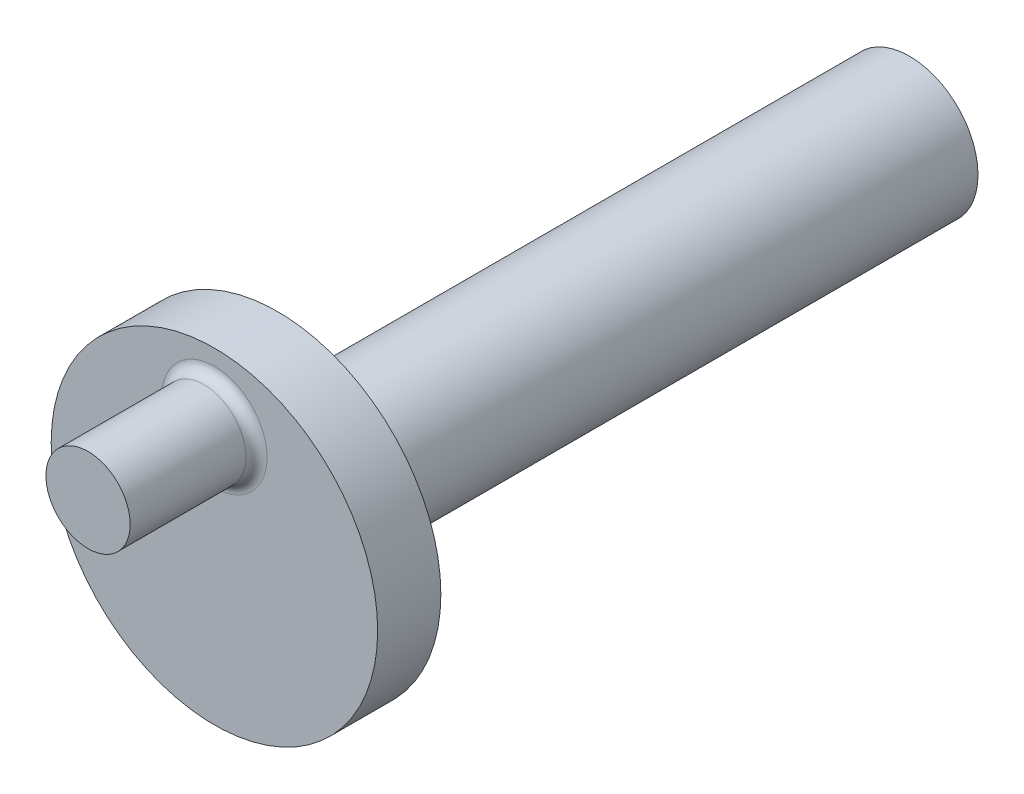
SolidWorks part; units mm, degrees
ref_plane "Front Plane" through (0, 0, 0) normal (0, 0, 1) x (1, 0, 0)
ref_plane "Top Plane" through (0, 0, 0) normal (0, 1, 0) x (1, 0, 0)
ref_plane "Right Plane" through (0, 0, 0) normal (1, 0, 0) x (0, 0, -1)
sketch "Sketch1" plane through (0, 0, 0) normal (0, 0, 1) x (1, 0, 0)
  line L0 (0, -17.05) -> (0, 17.05) construction
  circle A0 centre (0, 0) radius 15.5
  circle A1 centre (0, 9) radius 4
  dimension "D1" = 31
  dimension "D3" = 8
extrude "Boss-Extrude2" add sketch "Sketch1" along normal mid plane 6 contours A0
extrude "Boss-Extrude3" add sketch "Sketch1<6>" along normal blind 12 from surface contours A1 starting at face at (15.5, 0, 3)
sketch "Sketch1<6>" plane through (0, 0, 0) normal (0, 0, 1) x (1, 0, 0) same geometry as "Sketch1"
sketch "Sketch2" plane through (0, 0, -3) normal (0, 0, -1) x (-1, 0, 0)
  circle A0 centre (0, 0) radius 6.5
  dimension "D1" = 13
extrude "Boss-Extrude4" add sketch "Sketch2" along normal blind 60
fillet "Fillet1" radius 1 2 edges at (-6.5, 0, -3) (4, 9, 3)
